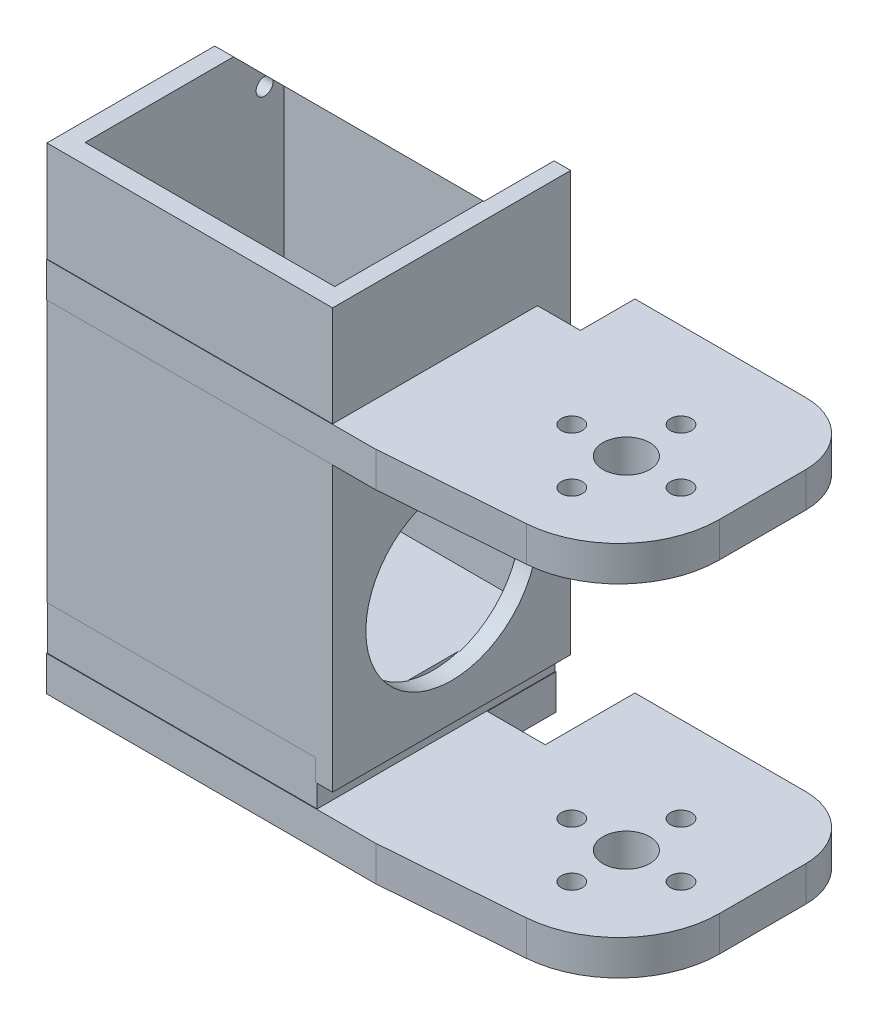
SolidWorks part; units mm, degrees
ref_plane "Front Plane" through (0, 0, 0) normal (0, 0, 1) x (1, 0, 0)
ref_plane "Top Plane" through (0, 0, 0) normal (0, 1, 0) x (1, 0, 0)
ref_plane "Right Plane" through (0, 0, 0) normal (1, 0, 0) x (0, 0, -1)
ref_plane "PY_m23_125" through (0, -23.125, 0) normal (0, 1, 0) x (1, 0, 0)
sketch "S_prism1" plane through (0, -23.125, 0) normal (0, 1, 0) x (1, 0, 0)
  line L0 (13, 10) -> (13, -1.0582)
  line L1 (1.0937, -13.9199) -> (-16.9, -15.31)
  line L2 (-16.9, -15.31) -> (-16.9, 18)
  line L3 (-16.9, 18) -> (5, 18)
  arc A0 (5, 18) -> (13, 10) centre (5.0002, 10.0002) cw
  arc A1 (13, -1.0582) -> (1.0937, -13.9199) centre (0.0999, -1.0582) cw
extrude "Boss_1" add sketch "S_prism1" along normal blind 4.5
ref_plane "PY_p18_625" through (0, 18.625, 0) normal (0, 1, 0) x (1, 0, 0)
sketch "S_cyl2" plane through (0, 18.625, 0) normal (0, 1, 0) x (1, 0, 0)
  circle A0 centre (0, 0) radius 9
  dimension "D1_S_cyl2" = 18
extrude "Boss_2" add sketch "S_cyl2" along normal blind 2
ref_plane "PY_p20_625" through (0, 20.625, 0) normal (0, 1, 0) x (1, 0, 0)
sketch "S_prism3" plane through (0, 20.625, 0) normal (0, 1, 0) x (1, 0, 0)
  line L0 (13, 10) -> (13, -1.0582)
  line L1 (1.0937, -13.9199) -> (-16.9, -15.31)
  line L2 (-16.9, -15.31) -> (-16.9, 18)
  line L3 (-16.9, 18) -> (5, 18)
  arc A0 (5, 18) -> (13, 10) centre (5.0002, 10.0002) cw
  arc A1 (13, -1.0582) -> (1.0937, -13.9199) centre (0.0999, -1.0582) cw
extrude "Boss_3" add sketch "S_prism3" along normal blind 4.5
sketch "S_prism4" plane through (0, -23.125, 0) normal (0, 1, 0) x (1, 0, 0)
  line L0 (-24.575, 6.5) -> (-16.8, 6.5)
  line L1 (-16.8, 6.5) -> (-16.8, -15.31)
  line L2 (-16.8, -15.31) -> (-24.575, -15.31)
  line L3 (-24.575, -15.31) -> (-24.575, 6.5)
extrude "Boss_4" add sketch "S_prism4" along normal blind 4.5
sketch "S_prism5" plane through (0, -23.125, 0) normal (0, 1, 0) x (1, 0, 0)
  line L0 (-59.025, -12.71) -> (-16.8, -12.71)
  line L1 (-16.8, -12.71) -> (-16.8, -15.31)
  line L2 (-16.8, -15.31) -> (-59.025, -15.31)
  line L3 (-59.025, -15.31) -> (-59.025, -12.71)
extrude "Boss_5" add sketch "S_prism5" along normal blind 4.5
sketch "S_prism6" plane through (0, -23.125, 0) normal (0, 1, 0) x (1, 0, 0)
  line L0 (-59.025, 15.31) -> (-24.325, 15.31)
  line L1 (-24.325, 15.31) -> (-24.325, -15.31)
  line L2 (-24.325, -15.31) -> (-59.025, -15.31)
  line L3 (-59.025, -15.31) -> (-59.025, 15.31)
extrude "Boss_6" add sketch "S_prism6" along normal blind 4.5
sketch "S_prism7" plane through (0, 20.625, 0) normal (0, 1, 0) x (1, 0, 0)
  line L0 (-24.575, 11) -> (-16.8, 11)
  line L1 (-16.8, 11) -> (-16.8, -15.31)
  line L2 (-16.8, -15.31) -> (-24.575, -15.31)
  line L3 (-24.575, -15.31) -> (-24.575, 11)
extrude "Boss_7" add sketch "S_prism7" along normal blind 4.5
sketch "S_prism8" plane through (0, 20.625, 0) normal (0, 1, 0) x (1, 0, 0)
  line L0 (-59.025, -12.71) -> (-16.8, -12.71)
  line L1 (-16.8, -12.71) -> (-16.8, -15.31)
  line L2 (-16.8, -15.31) -> (-59.025, -15.31)
  line L3 (-59.025, -15.31) -> (-59.025, -12.71)
extrude "Boss_8" add sketch "S_prism8" along normal blind 4.5
ref_plane "PZ_m15_260" through (0, 0, -15.26) normal (0, 0, 1) x (1, 0, 0)
sketch "S_box9" plane through (0, 0, -15.26) normal (0, 0, 1) x (1, 0, 0)
  line L0 (-59.025, -13.01) -> (-24.625, -13.01)
  line L1 (-24.625, -13.01) -> (-24.625, -10.51)
  line L2 (-24.625, -10.51) -> (-59.025, -10.51)
  line L3 (-59.025, -10.51) -> (-59.025, -13.01)
  dimension "P1" = 59.025
  dimension "P2" = 13.01
  dimension "P3" = 24.625
  dimension "P4" = 13.01
  dimension "P5" = 24.625
  dimension "P6" = 10.51
  dimension "P7" = 59.025
  dimension "P8" = 10.51
extrude "Boss_9" add sketch "S_box9" along normal blind 30.52
sketch "S_box10" plane through (0, 0, -15.26) normal (0, 0, 1) x (1, 0, 0)
  line L0 (-59.025, -13.01) -> (-24.625, -13.01)
  line L1 (-24.625, -13.01) -> (-24.625, 38.01)
  line L2 (-24.625, 38.01) -> (-59.025, 38.01)
  line L3 (-59.025, 38.01) -> (-59.025, -13.01)
  dimension "P1" = 59.025
  dimension "P2" = 13.01
  dimension "P3" = 24.625
  dimension "P4" = 13.01
  dimension "P5" = 24.625
  dimension "P6" = 38.01
  dimension "P7" = 59.025
  dimension "P8" = 38.01
extrude "Boss_10" add sketch "S_box10" along normal blind 2.5
ref_plane "PZ_p12_760" through (0, 0, 12.76) normal (0, 0, 1) x (1, 0, 0)
sketch "S_box11" plane through (0, 0, 12.76) normal (0, 0, 1) x (1, 0, 0)
  line L0 (-59.025, -13.01) -> (-24.625, -13.01)
  line L1 (-24.625, -13.01) -> (-24.625, 38.01)
  line L2 (-24.625, 38.01) -> (-59.025, 38.01)
  line L3 (-59.025, 38.01) -> (-59.025, -13.01)
  dimension "P1" = 59.025
  dimension "P2" = 13.01
  dimension "P3" = 24.625
  dimension "P4" = 13.01
  dimension "P5" = 24.625
  dimension "P6" = 38.01
  dimension "P7" = 59.025
  dimension "P8" = 38.01
extrude "Boss_11" add sketch "S_box11" along normal blind 2.5
sketch "S_box12" plane through (0, 0, -15.26) normal (0, 0, 1) x (1, 0, 0)
  line L0 (-59.025, -13.01) -> (-56.625, -13.01)
  line L1 (-56.625, -13.01) -> (-56.625, 38.01)
  line L2 (-56.625, 38.01) -> (-59.025, 38.01)
  line L3 (-59.025, 38.01) -> (-59.025, -13.01)
  dimension "P1" = 59.025
  dimension "P2" = 13.01
  dimension "P3" = 56.625
  dimension "P4" = 13.01
  dimension "P5" = 56.625
  dimension "P6" = 38.01
  dimension "P7" = 59.025
  dimension "P8" = 38.01
extrude "Boss_12" add sketch "S_box12" along normal blind 30.52
sketch "S_box13" plane through (0, 0, -15.26) normal (0, 0, 1) x (1, 0, 0)
  line L0 (-24.625, -15.76) -> (-22.4, -15.76)
  line L1 (-22.4, -15.76) -> (-22.4, 38.01)
  line L2 (-22.4, 38.01) -> (-24.625, 38.01)
  line L3 (-24.625, 38.01) -> (-24.625, -15.76)
  dimension "P1" = 24.625
  dimension "P2" = 15.76
  dimension "P3" = 22.4
  dimension "P4" = 15.76
  dimension "P5" = 22.4
  dimension "P6" = 38.01
  dimension "P7" = 24.625
  dimension "P8" = 38.01
extrude "Boss_13" add sketch "S_box13" along normal blind 30.52
ref_plane "PZ_m15_240" through (0, 0, -15.24) normal (0, 0, 1) x (1, 0, 0)
sketch "S_box14" plane through (0, 0, -15.24) normal (0, 0, 1) x (1, 0, 0)
  line L0 (-58.955, -18.725) -> (-24.395, -18.725)
  line L1 (-24.395, -18.725) -> (-24.395, -12.9)
  line L2 (-24.395, -12.9) -> (-58.955, -12.9)
  line L3 (-58.955, -12.9) -> (-58.955, -18.725)
  dimension "P1" = 58.955
  dimension "P2" = 18.725
  dimension "P3" = 24.395
  dimension "P4" = 18.725
  dimension "P5" = 24.395
  dimension "P6" = 12.9
  dimension "P7" = 58.955
  dimension "P8" = 12.9
extrude "Boss_14" add sketch "S_box14" along normal blind 30.48
ref_plane "PY_m23_225" through (0, -23.225, 0) normal (0, 1, 0) x (1, 0, 0)
sketch "S_hole15" plane through (0, -23.225, 0) normal (0, 1, 0) x (1, 0, 0)
  circle A0 centre (0, 0) radius 3
  dimension "D1_S_hole15" = 6
extrude "Hole_15" cut sketch "S_hole15" along normal blind 4.7
sketch "S_hole16" plane through (0, -23.225, 0) normal (0, 1, 0) x (1, 0, 0)
  circle A0 centre (7, 0) radius 1.35
  dimension "D1_S_hole16" = 2.7
  dimension "P2" = 7
extrude "Hole_16" cut sketch "S_hole16" along normal blind 4.7
sketch "S_hole17" plane through (0, -23.225, 0) normal (0, 1, 0) x (1, 0, 0)
  circle A0 centre (0, -7) radius 1.35
  dimension "D1_S_hole17" = 2.7
  dimension "P2" = 7
extrude "Hole_17" cut sketch "S_hole17" along normal blind 4.7
sketch "S_hole18" plane through (0, -23.225, 0) normal (0, 1, 0) x (1, 0, 0)
  circle A0 centre (-7, 0) radius 1.35
  dimension "D1_S_hole18" = 2.7
  dimension "P2" = 7
extrude "Hole_18" cut sketch "S_hole18" along normal blind 4.7
sketch "S_hole19" plane through (0, -23.225, 0) normal (0, 1, 0) x (1, 0, 0)
  circle A0 centre (0, 7) radius 1.35
  dimension "D1_S_hole19" = 2.7
  dimension "P2" = 7
extrude "Hole_19" cut sketch "S_hole19" along normal blind 4.7
ref_plane "PY_p18_525" through (0, 18.525, 0) normal (0, 1, 0) x (1, 0, 0)
sketch "S_hole20" plane through (0, 18.525, 0) normal (0, 1, 0) x (1, 0, 0)
  circle A0 centre (0, 0) radius 3
  dimension "D1_S_hole20" = 6
extrude "Hole_20" cut sketch "S_hole20" along normal blind 6.7
sketch "S_hole21" plane through (0, 18.525, 0) normal (0, 1, 0) x (1, 0, 0)
  circle A0 centre (7, 0) radius 1.35
  dimension "D1_S_hole21" = 2.7
  dimension "P2" = 7
extrude "Hole_21" cut sketch "S_hole21" along normal blind 6.7
sketch "S_hole22" plane through (0, 18.525, 0) normal (0, 1, 0) x (1, 0, 0)
  circle A0 centre (0, -7) radius 1.35
  dimension "D1_S_hole22" = 2.7
  dimension "P2" = 7
extrude "Hole_22" cut sketch "S_hole22" along normal blind 6.7
sketch "S_hole23" plane through (0, 18.525, 0) normal (0, 1, 0) x (1, 0, 0)
  circle A0 centre (-7, 0) radius 1.35
  dimension "D1_S_hole23" = 2.7
  dimension "P2" = 7
extrude "Hole_23" cut sketch "S_hole23" along normal blind 6.7
sketch "S_hole24" plane through (0, 18.525, 0) normal (0, 1, 0) x (1, 0, 0)
  circle A0 centre (0, 7) radius 1.35
  dimension "D1_S_hole24" = 2.7
  dimension "P2" = 7
extrude "Hole_24" cut sketch "S_hole24" along normal blind 6.7
ref_plane "PX_m59_125" through (-59.125, 0, 0) normal (1, 0, 0) x (0, 0, -1)
sketch "S_hole25" plane through (-59.125, 0, 0) normal (1, 0, 0) x (0, 0, -1)
  circle A0 centre (0, 0) radius 11
  dimension "D1_S_hole25" = 22
extrude "Hole_25" cut sketch "S_hole25" along normal blind 2.6
sketch "S_hole26" plane through (-59.125, 0, 0) normal (1, 0, 0) x (0, 0, -1)
  circle A0 centre (-10.25, 8.3) radius 1.1
  dimension "D1_S_hole26" = 2.2
  dimension "P2" = 10.25
  dimension "P3" = 8.3
extrude "Hole_26" cut sketch "S_hole26" along normal blind 2.6
sketch "S_hole27" plane through (-59.125, 0, 0) normal (1, 0, 0) x (0, 0, -1)
  circle A0 centre (10.25, 32.75) radius 1.1
  dimension "D1_S_hole27" = 2.2
  dimension "P2" = 10.25
  dimension "P3" = 32.75
extrude "Hole_27" cut sketch "S_hole27" along normal blind 2.6
sketch "S_hole28" plane through (-59.125, 0, 0) normal (1, 0, 0) x (0, 0, -1)
  circle A0 centre (-10.25, 32.75) radius 1.1
  dimension "D1_S_hole28" = 2.2
  dimension "P2" = 10.25
  dimension "P3" = 32.75
extrude "Hole_28" cut sketch "S_hole28" along normal blind 2.6
ref_plane "PX_m24_725" through (-24.725, 0, 0) normal (1, 0, 0) x (0, 0, -1)
sketch "S_hole29" plane through (-24.725, 0, 0) normal (1, 0, 0) x (0, 0, -1)
  circle A0 centre (0, 0) radius 11
  dimension "D1_S_hole29" = 22
extrude "Hole_29" cut sketch "S_hole29" along normal blind 2.425
sketch "S_pcut30" plane through (-59.125, 0, 0) normal (1, 0, 0) x (0, 0, -1)
  line L0 (15.86, 38.61) -> (15.86, 28.41)
  line L1 (15.86, 28.41) -> (5.66, 38.61)
  line L2 (5.66, 38.61) -> (15.86, 38.61)
extrude "Cut_30" cut sketch "S_pcut30" along normal blind 34.6
equation "\"plate_t\" = 3"
equation "\"clearance\" = 0.4"
